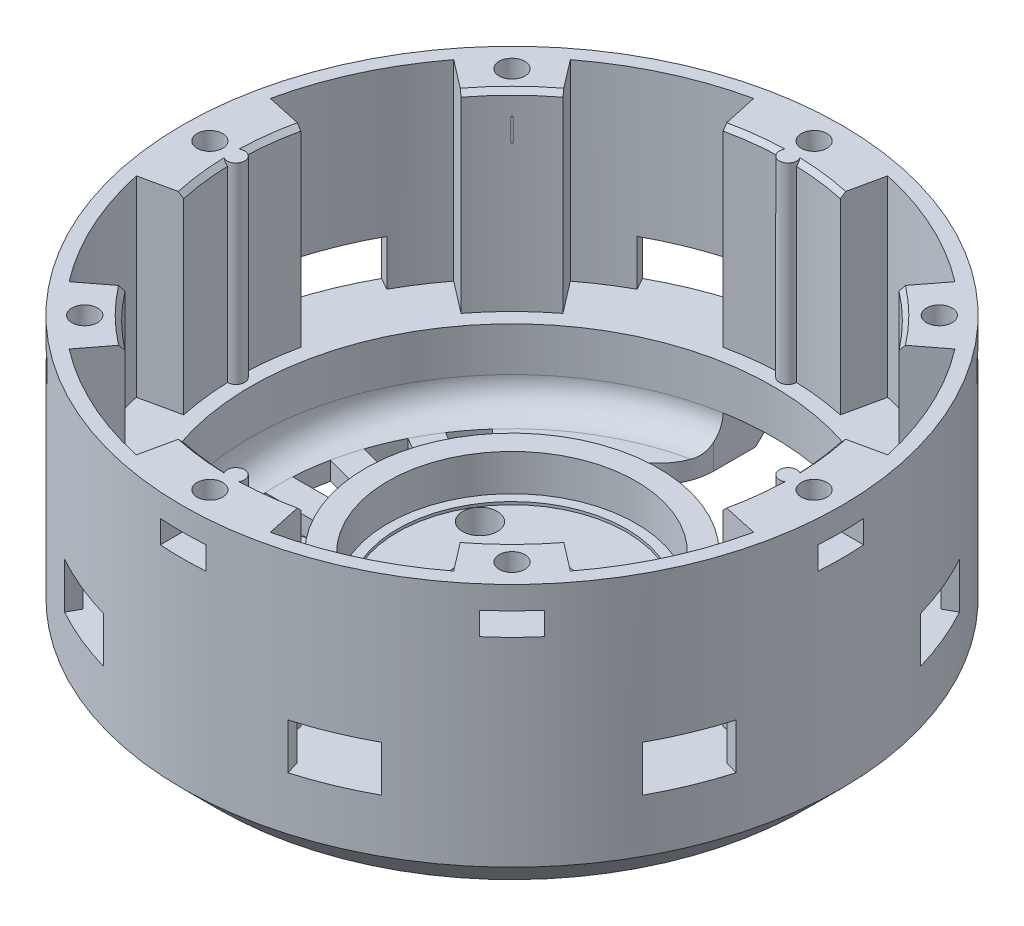
SolidWorks part; units mm, degrees
ref_plane "Front Plane" through (0, 0, 0) normal (0, 0, 1) x (1, 0, 0)
ref_plane "Top Plane" through (0, 0, 0) normal (0, 1, 0) x (1, 0, 0)
ref_plane "Right Plane" through (0, 0, 0) normal (1, 0, 0) x (0, 0, -1)
sketch "Sketch1" plane through (0, 0, 0) normal (0, 1, 0) x (1, 0, 0)
  circle A0 centre (0, 0) radius 36
  dimension "D1" = 72
extrude "Boss-Extrude1" add sketch "Sketch1" along normal blind 4
sketch "Sketch6" plane through (0, 4, 0) normal (0, 1, 0) x (1, 0, 0)
  circle A0 centre (0, 0) radius 16
  circle A1 centre (0, 0) radius 12.5
  dimension "D1" = 32
  dimension "D2" = 25
extrude "Boss-Extrude4" add sketch "Sketch6" along normal blind 0.3
sketch "Sketch7" plane through (0, 4.3, 0) normal (0, 1, 0) x (1, 0, 0)
  circle A0 centre (0, 0) radius 13.55
  circle A1 centre (0, 0) radius 16
  circle A2 centre (0, 0) radius 16
  dimension "D2" = 27.1
  dimension "D1" = 0
extrude "Boss-Extrude5" add sketch "Sketch7" along normal blind 4
sketch "Sketch2" plane through (0, 4, 0) normal (0, 1, 0) x (1, 0, 0)
  circle A0 centre (0, 0) radius 28.5
  circle A1 centre (0, 0) radius 36 construction
  circle A2 centre (0, 0) radius 36
  dimension "D1" = 57
extrude "Boss-Extrude2" add sketch "Sketch2" along normal offset from surface (5.8 mm away) 1.5 up to face at (0, 8.3, 16) offset beyond the face yes
sketch "Sketch3" plane through (0, 9.8, 0) normal (0, 1, 0) x (1, 0, 0)
  arc A0 (-0.9499, 30.135) -> (-30.135, 0.9499) centre (0, 0) ccw
  circle A1 centre (0, 0) radius 36 construction
  circle A2 centre (0, 0) radius 36
  arc A3 (-0.9499, 30.135) -> (0.9499, 30.135) centre (0, 30.15) ccw
  arc A4 (30.135, 0.9499) -> (30.135, -0.9499) centre (30.15, 0) ccw
  arc A5 (0.9499, -30.135) -> (-0.9499, -30.135) centre (0, -30.15) ccw
  arc A6 (-30.135, -0.9499) -> (-30.135, 0.9499) centre (-30.15, 0) ccw
  arc A7 (-30.135, -0.9499) -> (-0.9499, -30.135) centre (0, 0) ccw
  arc A8 (0.9499, -30.135) -> (30.135, -0.9499) centre (0, 0) ccw
  arc A9 (30.135, 0.9499) -> (0.9499, 30.135) centre (0, 0) ccw
  point P21 (0, 0)
  dimension "60.15" = 60.3
  dimension "D2" = 0.95
  dimension "D3" = 4
extrude "Boss-Extrude3" add sketch "Sketch3" along normal blind 20.95
sketch "Sketch8" plane through (0, 0, 0) normal (0, -1, 0) x (1, 0, 0)
  line L0 (0, 0) -> (0, -7.5) construction
  line L1 (-11, 7.5) -> (11, 7.5) construction
  line L2 (-11, 7.5) -> (-11, -7.5) construction
  line L3 (-11, -7.5) -> (11, -7.5) construction
  line L4 (11, 7.5) -> (11, -7.5) construction
  line L5 (-11, 7.5) -> (11, -7.5) construction
  line L6 (-11, -7.5) -> (11, 7.5) construction
  line L7 (0, 0) -> (11, 0) construction
  circle A0 centre (0, 0) radius 5.75
  circle A1 centre (-9, -5.5) radius 1.905
  circle A2 centre (9, -5.5) radius 1.905
  circle A3 centre (-9, 5.5) radius 1.905
  circle A4 centre (9, 5.5) radius 1.905
  point P0 (0, 0)
  dimension "D3" = 11.5
  dimension "D6" = 3.81
  dimension "D1" = 15
  dimension "D2" = 22
  dimension "D4" = 9
  dimension "D5" = 5.5
extrude "Cut-Extrude1" cut sketch "Sketch8" against normal up to surface (4 mm away) up to face at (0, 4, 16)
sketch "Sketch9" plane through (0, 0, 0) normal (0, -1, 0) x (1, 0, 0)
  line L0 (11, 7.5) -> (11, -7.5) construction
  line L1 (-11, -11) -> (11, -11)
  line L2 (-11, -11) -> (-11, -21)
  line L3 (-11, -21) -> (11, -21) construction
  line L4 (11, -11) -> (11, -21)
  line L5 (-11, 7.5) -> (11, 7.5) construction
  line L6 (-11, 7.5) -> (-11, -7.5) construction
  line L7 (0, 0) -> (0, -36) construction
  line L8 (-5, -27) -> (-5, -35.6511)
  line L9 (5, -27) -> (5, -35.6511)
  circle A0 centre (0, 0) radius 36 construction
  arc A1 (-11, -21) -> (-5, -27) centre (-11, -27) cw
  arc A2 (11, -21) -> (5, -27) centre (11, -27) ccw
  arc A3 (-5, -35.6511) -> (5, -35.6511) centre (0, 0) ccw
  dimension "D1" = 28.5
  dimension "D2" = 10
  dimension "D3" = 5
extrude "Cut-Extrude2" cut sketch "Sketch9" against normal blind 3
sketch "Sketch10" plane through (0, 4, 0) normal (0, 1, 0) x (1, 0, 0)
  circle A0 centre (0, 0) radius 16 construction
  circle A1 centre (0, 0) radius 28.5
  circle A2 centre (0, 0) radius 28.5
  circle A3 centre (0, 0) radius 16
  dimension "D1" = 0
extrude "Cut-Extrude3" cut sketch "Sketch10" against normal blind 2
sketch "Sketch11" plane through (0, 0, 0) normal (0, -1, 0) x (1, 0, 0)
  line L0 (-11, -11) -> (-11, -21) construction
  line L1 (11, -11) -> (-11, -11)
  line L2 (11, -11) -> (11, -10)
  line L3 (11, -10) -> (-11, -10)
  line L4 (-11, -11) -> (-11, -10)
  dimension "D1" = 1
sketch "Sketch12" plane through (0, 3, 0) normal (0, -1, 0) x (1, 0, 0)
  line L3 (11, -11.619) -> (11, -11)
  line L4 (11, -11) -> (-11, -11)
  line L5 (-11, -11) -> (-11, -11.619)
  line L6 (11, -11.619) -> (11, -11)
  line L7 (11, -11) -> (-11, -11)
  line L8 (-11, -11) -> (-11, -11.619)
  arc A1 (-11, -11.619) -> (11, -11.619) centre (0, 0) ccw
  arc A2 (-11, -11.619) -> (11, -11.619) centre (0, 0) ccw
  dimension "D1" = 0
loft "Loft1" add profiles "Sketch11", "Sketch12" connector at (-11, 0, -11) connector at (-11, 3, -11.6189)
sketch "Sketch13" plane through (0, 30.75, 0) normal (0, 1, 0) x (1, 0, 0)
  line L0 (0, 0) -> (-25.4558, 25.4558) construction
  line L1 (-11, 7.5) -> (11, -7.5) construction
  line L2 (0, 0) -> (0, 36) construction
  line L3 (0, 0) -> (-7.6384, 35.1803) construction
  line L4 (0, 0) -> (-21.9154, 28.5607) construction
  line L5 (-21.0023, 27.3707) -> (-18.3542, 23.9196)
  line L6 (-7.3201, 33.7145) -> (-6.3972, 29.4635)
  line L7 (21.0023, 27.3707) -> (18.3542, 23.9196)
  line L8 (7.3201, 33.7145) -> (6.3972, 29.4635)
  line L9 (33.7145, 7.3201) -> (29.4635, 6.3972)
  line L10 (27.3707, 21.0023) -> (23.9196, 18.3542)
  line L11 (33.7145, -7.3201) -> (29.4635, -6.3972)
  line L12 (27.3707, -21.0023) -> (23.9196, -18.3542)
  line L13 (7.3201, -33.7145) -> (6.3972, -29.4635)
  line L14 (21.0023, -27.3707) -> (18.3542, -23.9196)
  line L15 (-7.3201, -33.7145) -> (-6.3972, -29.4635)
  line L16 (-21.0023, -27.3707) -> (-18.3542, -23.9196)
  line L17 (-33.7145, -7.3201) -> (-29.4635, -6.3972)
  line L18 (-27.3707, -21.0023) -> (-23.9196, -18.3542)
  line L19 (-33.7145, 7.3201) -> (-29.4635, 6.3972)
  line L20 (-27.3707, 21.0023) -> (-23.9196, 18.3542)
  circle A0 centre (0, 0) radius 36 construction
  arc A1 (-21.0023, 27.3707) -> (-7.3201, 33.7145) centre (0, 0) cw
  arc A2 (-0.9499, 30.135) -> (-30.135, 0.9499) centre (0, 0) ccw construction
  arc A3 (-18.3542, 23.9196) -> (-6.3972, 29.4635) centre (0, 0) cw
  arc A4 (21.0023, 27.3707) -> (7.3201, 33.7145) centre (0, 0) ccw
  arc A5 (18.3542, 23.9196) -> (6.3972, 29.4635) centre (0, 0) ccw
  arc A6 (23.9196, 18.3542) -> (29.4635, 6.3972) centre (0, 0) cw
  arc A7 (27.3707, 21.0023) -> (33.7145, 7.3201) centre (0, 0) cw
  arc A8 (27.3707, -21.0023) -> (33.7145, -7.3201) centre (0, 0) ccw
  arc A9 (23.9196, -18.3542) -> (29.4635, -6.3972) centre (0, 0) ccw
  arc A10 (18.3542, -23.9196) -> (6.3972, -29.4635) centre (0, 0) cw
  arc A11 (21.0023, -27.3707) -> (7.3201, -33.7145) centre (0, 0) cw
  arc A12 (-21.0023, -27.3707) -> (-7.3201, -33.7145) centre (0, 0) ccw
  arc A13 (-18.3542, -23.9196) -> (-6.3972, -29.4635) centre (0, 0) ccw
  arc A14 (-23.9196, -18.3542) -> (-29.4635, -6.3972) centre (0, 0) cw
  arc A15 (-27.3707, -21.0023) -> (-33.7145, -7.3201) centre (0, 0) cw
  arc A16 (-27.3707, 21.0023) -> (-33.7145, 7.3201) centre (0, 0) ccw
  arc A17 (-23.9196, 18.3542) -> (-29.4635, 6.3972) centre (0, 0) ccw
  point P50 (0, 0)
  dimension "D4" = 1.5
  dimension "D1" = 45
  dimension "D2" = 12.25
  dimension "D3" = 7.5
  dimension "D5" = 4
extrude "Cut-Extrude4" cut sketch "Sketch13" against normal up to surface (20.95 mm away) up to face at (0, 9.8, 28.5)
fillet "Fillet1" radius 3 2 edges at (0, 2, 16) (0, 2, 28.5)
chamfer "Chamfer3" distance 4 angle 45 1 edges at (0, 0, 36)
sketch "Sketch14" plane through (0, 2, 0) normal (0, 1, 0) x (1, 0, 0)
  line L0 (0, 0) -> (0, -25.5) construction
  line L1 (0, 0) -> (3.3284, -25.2818) construction
  line L2 (0, 0) -> (6.5999, -24.6311) construction
  line L3 (0, -25.5) -> (6.5999, -24.6311) construction
  line L4 (1.5, -18.9407) -> (1.5, -25.4558)
  line L5 (3.4533, -18.6835) -> (5.1396, -24.9767)
  line L6 (-1.5, -18.9407) -> (-1.5, -25.4558)
  line L7 (-3.4533, -18.6835) -> (-5.1396, -24.9767)
  line L8 (-6.3511, -17.9071) -> (-8.0373, -24.2002)
  line L9 (-8.1713, -17.1531) -> (-11.4289, -22.7954)
  line L10 (-10.7694, -15.6531) -> (-14.027, -21.2954)
  line L11 (-12.3324, -14.4538) -> (-16.9393, -19.0607)
  line L12 (-14.4538, -12.3324) -> (-19.0607, -16.9393)
  line L13 (-15.6531, -10.7694) -> (-21.2954, -14.027)
  line L14 (-17.1531, -8.1713) -> (-22.7954, -11.4289)
  line L15 (-17.9071, -6.3511) -> (-24.2002, -8.0373)
  line L16 (-18.6835, -3.4533) -> (-24.9767, -5.1396)
  line L17 (-18.9407, -1.5) -> (-25.4558, -1.5)
  line L18 (-18.9407, 1.5) -> (-25.4558, 1.5)
  line L19 (-18.6835, 3.4533) -> (-24.9767, 5.1396)
  line L20 (-17.9071, 6.3511) -> (-24.2002, 8.0373)
  line L21 (-17.1531, 8.1713) -> (-22.7954, 11.4289)
  line L22 (-15.6531, 10.7694) -> (-21.2954, 14.027)
  line L23 (-14.4538, 12.3324) -> (-19.0607, 16.9393)
  line L24 (-12.3324, 14.4538) -> (-16.9393, 19.0607) [skipped]
  line L25 (-10.7694, 15.6531) -> (-14.027, 21.2954) [skipped]
  line L26 (-8.1713, 17.1531) -> (-11.4289, 22.7954) [skipped]
  line L27 (-6.3511, 17.9071) -> (-8.0373, 24.2002) [skipped]
  line L28 (-3.4533, 18.6835) -> (-5.1396, 24.9767) [skipped]
  line L29 (-1.5, 18.9407) -> (-1.5, 25.4558) [skipped]
  line L30 (1.5, 18.9407) -> (1.5, 25.4558) [skipped]
  line L31 (3.4533, 18.6835) -> (5.1396, 24.9767) [skipped]
  line L32 (6.3511, 17.9071) -> (8.0373, 24.2002) [skipped]
  line L33 (8.1713, 17.1531) -> (11.4289, 22.7954) [skipped]
  line L34 (10.7694, 15.6531) -> (14.027, 21.2954) [skipped]
  line L35 (12.3324, 14.4538) -> (16.9393, 19.0607) [skipped]
  line L36 (14.4538, 12.3324) -> (19.0607, 16.9393)
  line L37 (15.6531, 10.7694) -> (21.2954, 14.027)
  line L38 (17.1531, 8.1713) -> (22.7954, 11.4289)
  line L39 (17.9071, 6.3511) -> (24.2002, 8.0373)
  line L40 (18.6835, 3.4533) -> (24.9767, 5.1396)
  line L41 (18.9407, 1.5) -> (25.4558, 1.5)
  line L42 (18.9407, -1.5) -> (25.4558, -1.5)
  line L43 (18.6835, -3.4533) -> (24.9767, -5.1396)
  line L44 (17.9071, -6.3511) -> (24.2002, -8.0373)
  line L45 (17.1531, -8.1713) -> (22.7954, -11.4289)
  line L46 (15.6531, -10.7694) -> (21.2954, -14.027)
  line L47 (14.4538, -12.3324) -> (19.0607, -16.9393)
  line L48 (12.3324, -14.4538) -> (16.9393, -19.0607)
  line L49 (10.7694, -15.6531) -> (14.027, -21.2954)
  line L50 (8.1713, -17.1531) -> (11.4289, -22.7954)
  line L51 (6.3511, -17.9071) -> (8.0373, -24.2002)
  arc A0 (-5.369, 24.9284) -> (5.369, 24.9284) centre (0, 0) ccw construction
  arc A1 (-11, 15.4919) -> (11, 15.4919) centre (0, 0) ccw construction
  arc A2 (1.5, -18.9407) -> (3.4533, -18.6835) centre (0, 0) ccw
  arc A3 (1.5, -25.4558) -> (5.1396, -24.9767) centre (0, 0) ccw
  arc A4 (-5.1396, -24.9767) -> (-1.5, -25.4558) centre (0, 0) ccw
  arc A5 (-3.4533, -18.6835) -> (-1.5, -18.9407) centre (0, 0) ccw
  arc A6 (-11.4289, -22.7954) -> (-8.0373, -24.2002) centre (0, 0) ccw
  arc A7 (-8.1713, -17.1531) -> (-6.3511, -17.9071) centre (0, 0) ccw
  arc A8 (-16.9393, -19.0607) -> (-14.027, -21.2954) centre (0, 0) ccw
  arc A9 (-12.3324, -14.4538) -> (-10.7694, -15.6531) centre (0, 0) ccw
  arc A10 (-21.2954, -14.027) -> (-19.0607, -16.9393) centre (0, 0) ccw
  arc A11 (-15.6531, -10.7694) -> (-14.4538, -12.3324) centre (0, 0) ccw
  arc A12 (-24.2002, -8.0373) -> (-22.7954, -11.4289) centre (0, 0) ccw
  arc A13 (-17.9071, -6.3511) -> (-17.1531, -8.1713) centre (0, 0) ccw
  arc A14 (-25.4558, -1.5) -> (-24.9767, -5.1396) centre (0, 0) ccw
  arc A15 (-18.9407, -1.5) -> (-18.6835, -3.4533) centre (0, 0) ccw
  arc A16 (-24.9767, 5.1396) -> (-25.4558, 1.5) centre (0, 0) ccw
  arc A17 (-18.6835, 3.4533) -> (-18.9407, 1.5) centre (0, 0) ccw
  arc A18 (-22.7954, 11.4289) -> (-24.2002, 8.0373) centre (0, 0) ccw
  arc A19 (-17.1531, 8.1713) -> (-17.9071, 6.3511) centre (0, 0) ccw
  arc A20 (-19.0607, 16.9393) -> (-21.2954, 14.027) centre (0, 0) ccw
  arc A21 (-14.4538, 12.3324) -> (-15.6531, 10.7694) centre (0, 0) ccw
  arc A22 (-14.027, 21.2954) -> (-16.9393, 19.0607) centre (0, 0) ccw [skipped]
  arc A23 (-10.7694, 15.6531) -> (-12.3324, 14.4538) centre (0, 0) ccw [skipped]
  arc A24 (-8.0373, 24.2002) -> (-11.4289, 22.7954) centre (0, 0) ccw [skipped]
  arc A25 (-6.3511, 17.9071) -> (-8.1713, 17.1531) centre (0, 0) ccw [skipped]
  arc A26 (-1.5, 25.4558) -> (-5.1396, 24.9767) centre (0, 0) ccw [skipped]
  arc A27 (-1.5, 18.9407) -> (-3.4533, 18.6835) centre (0, 0) ccw [skipped]
  arc A28 (5.1396, 24.9767) -> (1.5, 25.4558) centre (0, 0) ccw [skipped]
  arc A29 (3.4533, 18.6835) -> (1.5, 18.9407) centre (0, 0) ccw [skipped]
  arc A30 (11.4289, 22.7954) -> (8.0373, 24.2002) centre (0, 0) ccw [skipped]
  arc A31 (8.1713, 17.1531) -> (6.3511, 17.9071) centre (0, 0) ccw [skipped]
  arc A32 (16.9393, 19.0607) -> (14.027, 21.2954) centre (0, 0) ccw [skipped]
  arc A33 (12.3324, 14.4538) -> (10.7694, 15.6531) centre (0, 0) ccw [skipped]
  arc A34 (21.2954, 14.027) -> (19.0607, 16.9393) centre (0, 0) ccw
  arc A35 (15.6531, 10.7694) -> (14.4538, 12.3324) centre (0, 0) ccw
  arc A36 (24.2002, 8.0373) -> (22.7954, 11.4289) centre (0, 0) ccw
  arc A37 (17.9071, 6.3511) -> (17.1531, 8.1713) centre (0, 0) ccw
  arc A38 (25.4558, 1.5) -> (24.9767, 5.1396) centre (0, 0) ccw
  arc A39 (18.9407, 1.5) -> (18.6835, 3.4533) centre (0, 0) ccw
  arc A40 (24.9767, -5.1396) -> (25.4558, -1.5) centre (0, 0) ccw
  arc A41 (18.6835, -3.4533) -> (18.9407, -1.5) centre (0, 0) ccw
  arc A42 (22.7954, -11.4289) -> (24.2002, -8.0373) centre (0, 0) ccw
  arc A43 (17.1531, -8.1713) -> (17.9071, -6.3511) centre (0, 0) ccw
  arc A44 (19.0607, -16.9393) -> (21.2954, -14.027) centre (0, 0) ccw
  arc A45 (14.4538, -12.3324) -> (15.6531, -10.7694) centre (0, 0) ccw
  arc A46 (14.027, -21.2954) -> (16.9393, -19.0607) centre (0, 0) ccw
  arc A47 (10.7694, -15.6531) -> (12.3324, -14.4538) centre (0, 0) ccw
  arc A48 (8.0373, -24.2002) -> (11.4289, -22.7954) centre (0, 0) ccw
  arc A49 (6.3511, -17.9071) -> (8.1713, -17.1531) centre (0, 0) ccw
  point P9 (3.2999, -25.0656)
  point P88 (0, 0)
  point P113 (0, 0)
  dimension "D1" = 15
  dimension "D2" = 1.5
  dimension "D3" = 24
extrude "Cut-Extrude5" cut sketch "Sketch14" against normal through all
sketch "Sketch15" plane through (0, 30.75, 0) normal (0, 1, 0) x (1, 0, 0)
  circle A0 centre (0, 33) radius 1.4
  circle A1 centre (0, 0) radius 36 construction
  circle A2 centre (23.3345, 23.3345) radius 1.4
  circle A3 centre (33, 0) radius 1.4
  circle A4 centre (23.3345, -23.3345) radius 1.4
  circle A5 centre (0, -33) radius 1.4
  circle A6 centre (-23.3345, -23.3345) radius 1.4
  circle A7 centre (-33, 0) radius 1.4
  circle A8 centre (-23.3345, 23.3345) radius 1.4
  point P5 (0, 36)
  point P23 (0, 0)
  dimension "D1" = 2.8
  dimension "D2" = 3
  dimension "D3" = 8
extrude "Cut-Extrude6" cut sketch "Sketch15" against normal blind 5
chamfer "Chamfer4" distance 0.3 angle 45 1 edges at (0, 4, 5.75)
sketch "Sketch16" plane through (0, 3, 0) normal (0, -1, 0) x (1, 0, 0)
  line L0 (-5, -28.058) -> (-5, -34.641) construction
  line L1 (5, -28.058) -> (-5, -28.058)
  line L2 (5, -28.058) -> (5, -36)
  line L3 (5, -36) -> (-5, -36)
  line L4 (-5, -28.058) -> (-5, -36)
  circle A0 centre (0, 0) radius 36 construction
extrude "Cut-Extrude7" cut sketch "Sketch16" against normal blind 2
chamfer "Chamfer5" distance 0.5 angle 45 12 edges at (-21.3193, 30.75, 21.3193) (-3.6888, 30.75, 29.9235) (3.6888, 30.75, 29.9235) (21.3193, 30.75, 21.3193) (29.9235, 30.75, 3.6888) (29.9235, 30.75, -3.6888) (21.3193, 30.75, -21.3193) (3.6888, 30.75, -29.9235) (-3.6888, 30.75, -29.9235) (-21.3193, 30.75, -21.3193) (-29.9235, 30.75, 3.6888) (-29.9235, 30.75, -3.6888)
sketch "Sketch17" plane through (0, 9.8, 0) normal (0, 1, 0) x (1, 0, 0)
  line L0 (-17.3102, 31.5651) -> (-16.5889, 30.2499)
  line L1 (-9.6598, 33.1201) -> (-10.0798, 34.5601)
  line L2 (0, 0) -> (0, 36) construction
  line L3 (0, 0) -> (-13.2026, 31.8738) construction
  line L4 (10.0798, 34.5601) -> (9.6598, 33.1201)
  line L5 (16.5889, 30.2499) -> (17.3102, 31.5651)
  line L6 (31.5651, 17.3102) -> (30.2499, 16.5889)
  line L7 (33.1201, 9.6598) -> (34.5601, 10.0798)
  line L8 (34.5601, -10.0798) -> (33.1201, -9.6598)
  line L9 (30.2499, -16.5889) -> (31.5651, -17.3102)
  line L10 (17.3102, -31.5651) -> (16.5889, -30.2499)
  line L11 (9.6598, -33.1201) -> (10.0798, -34.5601)
  line L12 (-10.0798, -34.5601) -> (-9.6598, -33.1201)
  line L13 (-16.5889, -30.2499) -> (-17.3102, -31.5651)
  line L14 (-31.5651, -17.3102) -> (-30.2499, -16.5889)
  line L15 (-33.1201, -9.6598) -> (-34.5601, -10.0798)
  line L16 (-34.5601, 10.0798) -> (-33.1201, 9.6598)
  line L17 (-30.2499, 16.5889) -> (-31.5651, 17.3102)
  arc A0 (-16.5889, 30.2499) -> (-9.6598, 33.1201) centre (0, 0) cw
  arc A1 (-7.3201, 33.7145) -> (-21.0023, 27.3707) centre (0, 0) ccw construction
  arc A2 (-17.3102, 31.5651) -> (-10.0798, 34.5601) centre (0, 0) cw
  circle A3 centre (0, 0) radius 36 construction
  arc A4 (-7.3201, 33.7145) -> (-21.0023, 27.3707) centre (0, 0) ccw construction
  arc A5 (9.6598, 33.1201) -> (16.5889, 30.2499) centre (0, 0) cw
  arc A6 (10.0798, 34.5601) -> (17.3102, 31.5651) centre (0, 0) cw
  arc A7 (30.2499, 16.5889) -> (33.1201, 9.6598) centre (0, 0) cw
  arc A8 (31.5651, 17.3102) -> (34.5601, 10.0798) centre (0, 0) cw
  arc A9 (33.1201, -9.6598) -> (30.2499, -16.5889) centre (0, 0) cw
  arc A10 (34.5601, -10.0798) -> (31.5651, -17.3102) centre (0, 0) cw
  arc A11 (16.5889, -30.2499) -> (9.6598, -33.1201) centre (0, 0) cw
  arc A12 (17.3102, -31.5651) -> (10.0798, -34.5601) centre (0, 0) cw
  arc A13 (-9.6598, -33.1201) -> (-16.5889, -30.2499) centre (0, 0) cw
  arc A14 (-10.0798, -34.5601) -> (-17.3102, -31.5651) centre (0, 0) cw
  arc A15 (-30.2499, -16.5889) -> (-33.1201, -9.6598) centre (0, 0) cw
  arc A16 (-31.5651, -17.3102) -> (-34.5601, -10.0798) centre (0, 0) cw
  arc A17 (-33.1201, 9.6598) -> (-30.2499, 16.5889) centre (0, 0) cw
  arc A18 (-34.5601, 10.0798) -> (-31.5651, 17.3102) centre (0, 0) cw
  point P48 (0, 0)
  dimension "D1" = 22.5
  dimension "D2" = 7.5
  dimension "D3" = 8
extrude "Cut-Extrude8" cut sketch "Sketch17" along normal blind 5
sketch "Sketch18" plane through (0, 25.75, 0) normal (0, 1, 0) x (1, 0, 0)
  line L0 (-2.5, 34.4434) -> (-2.5, 36)
  line L1 (0, 35.8868) -> (-2.5, 34.4434) construction
  line L2 (-2.5, 34.4434) -> (-2.5, 31.5566)
  line L3 (-2.5, 31.5566) -> (0, 30.1132)
  line L4 (0, 30.1132) -> (2.5, 31.5566)
  line L5 (2.5, 31.5566) -> (2.5, 34.4434)
  line L6 (2.5, 34.4434) -> (0, 35.8868) construction
  line L7 (-2.5, 36) -> (2.5, 36)
  line L8 (2.5, 36) -> (2.5, 34.4434)
  line L9 (23.6881, 27.2236) -> (27.2236, 23.6881)
  line L10 (27.2236, 23.6881) -> (26.1229, 22.5874)
  line L11 (24.0817, 20.5461) -> (26.1229, 22.5874)
  line L12 (21.2933, 21.2933) -> (24.0817, 20.5461)
  line L13 (20.5461, 24.0817) -> (21.2933, 21.2933)
  line L14 (22.5874, 26.1229) -> (20.5461, 24.0817)
  line L15 (22.5874, 26.1229) -> (23.6881, 27.2236)
  line L16 (36, 2.5) -> (36, -2.5)
  line L17 (36, -2.5) -> (34.4434, -2.5)
  line L18 (31.5566, -2.5) -> (34.4434, -2.5)
  line L19 (30.1132, 0) -> (31.5566, -2.5)
  line L20 (31.5566, 2.5) -> (30.1132, 0)
  line L21 (34.4434, 2.5) -> (31.5566, 2.5)
  line L22 (34.4434, 2.5) -> (36, 2.5)
  line L23 (27.2236, -23.6881) -> (23.6881, -27.2236)
  line L24 (23.6881, -27.2236) -> (22.5874, -26.1229)
  line L25 (20.5461, -24.0817) -> (22.5874, -26.1229)
  line L26 (21.2933, -21.2933) -> (20.5461, -24.0817)
  line L27 (24.0817, -20.5461) -> (21.2933, -21.2933)
  line L28 (26.1229, -22.5874) -> (24.0817, -20.5461)
  line L29 (26.1229, -22.5874) -> (27.2236, -23.6881)
  line L30 (2.5, -36) -> (-2.5, -36)
  line L31 (-2.5, -36) -> (-2.5, -34.4434)
  line L32 (-2.5, -31.5566) -> (-2.5, -34.4434)
  line L33 (0, -30.1132) -> (-2.5, -31.5566)
  line L34 (2.5, -31.5566) -> (0, -30.1132)
  line L35 (2.5, -34.4434) -> (2.5, -31.5566)
  line L36 (2.5, -34.4434) -> (2.5, -36)
  line L37 (-23.6881, -27.2236) -> (-27.2236, -23.6881)
  line L38 (-27.2236, -23.6881) -> (-26.1229, -22.5874)
  line L39 (-24.0817, -20.5461) -> (-26.1229, -22.5874)
  line L40 (-21.2933, -21.2933) -> (-24.0817, -20.5461)
  line L41 (-20.5461, -24.0817) -> (-21.2933, -21.2933)
  line L42 (-22.5874, -26.1229) -> (-20.5461, -24.0817)
  line L43 (-22.5874, -26.1229) -> (-23.6881, -27.2236)
  line L44 (-36, -2.5) -> (-36, 2.5)
  line L45 (-36, 2.5) -> (-34.4434, 2.5)
  line L46 (-31.5566, 2.5) -> (-34.4434, 2.5)
  line L47 (-30.1132, 0) -> (-31.5566, 2.5)
  line L48 (-31.5566, -2.5) -> (-30.1132, 0)
  line L49 (-34.4434, -2.5) -> (-31.5566, -2.5)
  line L50 (-34.4434, -2.5) -> (-36, -2.5)
  line L51 (-27.2236, 23.6881) -> (-23.6881, 27.2236)
  line L52 (-23.6881, 27.2236) -> (-22.5874, 26.1229)
  line L53 (-20.5461, 24.0817) -> (-22.5874, 26.1229)
  line L54 (-21.2933, 21.2933) -> (-20.5461, 24.0817)
  line L55 (-24.0817, 20.5461) -> (-21.2933, 21.2933)
  line L56 (-26.1229, 22.5874) -> (-24.0817, 20.5461)
  line L57 (-26.1229, 22.5874) -> (-27.2236, 23.6881)
  circle A0 centre (0, 33) radius 2.5 construction
  circle A1 centre (0, 0) radius 36 construction
  point P65 (0, 0)
  dimension "D1" = 5
  dimension "D2" = 8
extrude "Cut-Extrude9" cut sketch "Sketch18" along normal blind 2.5
sketch "Sketch19" plane through (0, 0, 0) normal (0, -1, 0) x (1, 0, 0)
  line L1 (-3.05, -1.833) -> (5.45, -1.833)
  line L2 (-3.05, -1.833) -> (-3.05, -16)
  line L3 (-3.05, -16) -> (5.45, -16)
  line L4 (5.45, -1.833) -> (5.45, -16)
  circle A0 centre (0, 0) radius 5.75 construction
  arc A1 (-11, -11.619) -> (11, -11.619) centre (0, 0) ccw construction
  point P4 (0, 0)
  point P7 (0, 0)
  point P8 (1.2, -1.833)
  dimension "D1" = 8.5
  dimension "D2" = 1.2
extrude "Cut-Extrude10" cut sketch "Sketch19" against normal blind 2
